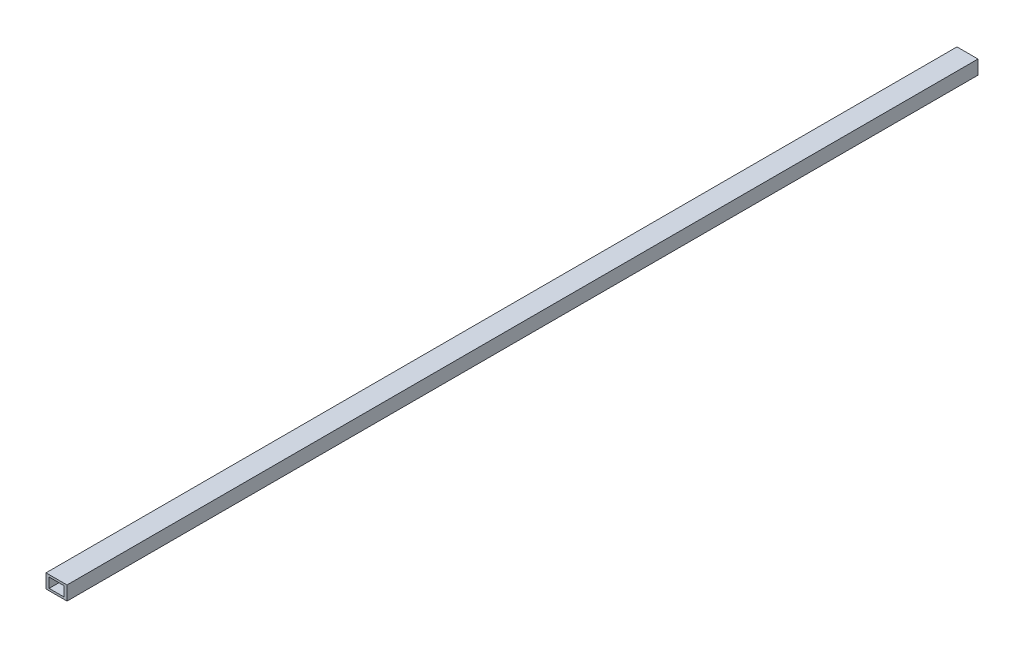
SolidWorks part; units mm, degrees
ref_plane "前视基准面" through (0, 0, 0) normal (0, 0, 1) x (1, 0, 0)
ref_plane "上视基准面" through (0, 0, 0) normal (0, 1, 0) x (1, 0, 0)
ref_plane "右视基准面" through (0, 0, 0) normal (1, 0, 0) x (0, 0, -1)
other "Configuration Table"
sketch "草图1" plane through (0, 0, 0) normal (0, 0, 1) x (1, 0, 0)
  line L1 (-7.5, 5) -> (7.5, 5)
  line L2 (-7.5, 5) -> (-7.5, -5)
  line L3 (-7.5, -5) -> (7.5, -5)
  line L4 (7.5, 5) -> (7.5, -5)
  line L5 (-7.5, 5) -> (7.5, -5) construction
  line L6 (-7.5, -5) -> (7.5, 5) construction
  line L7 (-5.25, 3.5) -> (5.25, 3.5)
  line L8 (-5.25, 3.5) -> (-5.25, -3.5)
  line L9 (-5.25, -3.5) -> (5.25, -3.5)
  line L10 (5.25, 3.5) -> (5.25, -3.5)
  line L11 (-5.25, 3.5) -> (5.25, -3.5) construction
  line L12 (-5.25, -3.5) -> (5.25, 3.5) construction
  point P0 (0, 0)
  point P5 (0, 0)
  dimension "D1" = 10
  dimension "D2" = 1.5
  dimension "D3" = 15
extrude "凸台-拉伸1" add sketch "草图1" along normal blind 650
